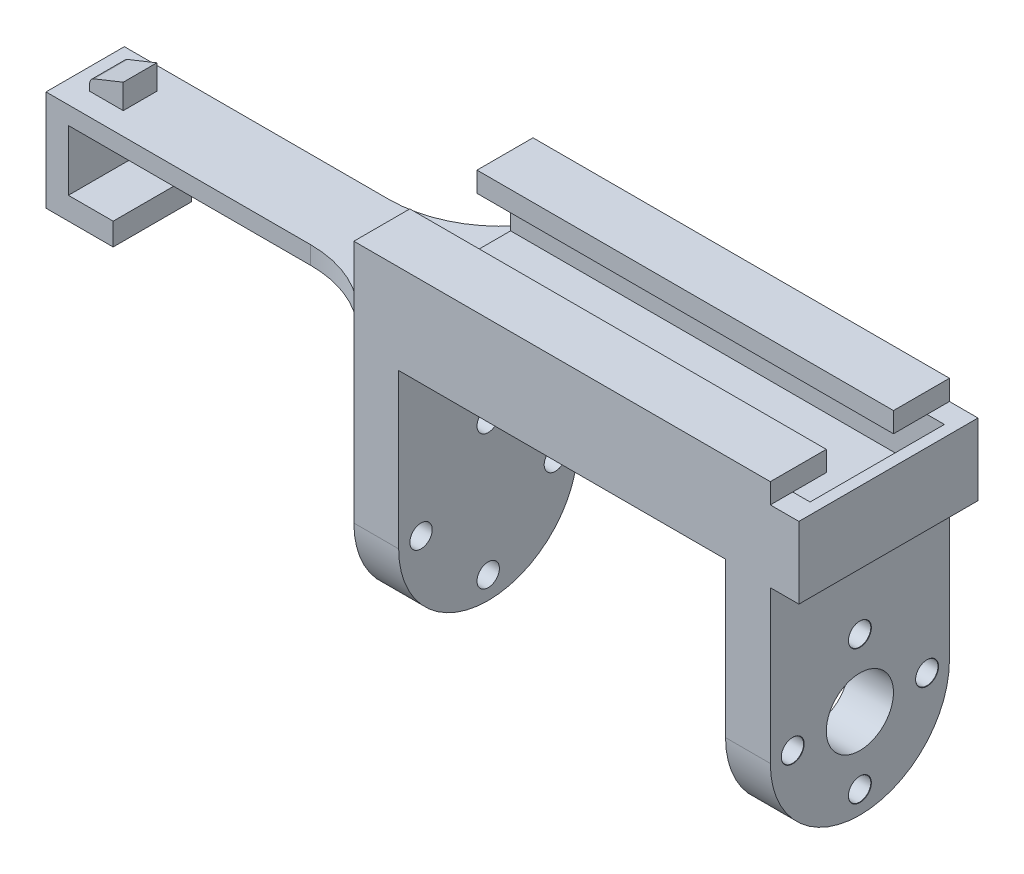
SolidWorks part; units mm, degrees
ref_plane "Front Plane" through (0, 0, 0) normal (0, 0, 1) x (1, 0, 0)
ref_plane "Top Plane" through (0, 0, 0) normal (0, 1, 0) x (1, 0, 0)
ref_plane "Right Plane" through (0, 0, 0) normal (1, 0, 0) x (0, 0, -1)
sketch "Sketch1" plane through (0, 0, 0) normal (0, 0, 1) x (1, 0, 0)
  line L1 (-18.6, 18) -> (18.6, 18)
  line L2 (-18.6, 18) -> (-18.6, -18)
  line L3 (-18.6, -18) -> (18.6, -18)
  line L4 (18.6, 18) -> (18.6, -18)
  line L5 (-18.6, 18) -> (18.6, -18) construction
  line L6 (-18.6, -18) -> (18.6, 18) construction
  line L7 (-14.6, -18) -> (14.6, -18)
  line L8 (-14.6, -18) -> (-14.6, 10)
  line L9 (-14.6, 10) -> (14.6, 10)
  line L10 (14.6, -18) -> (14.6, 10)
  point P0 (0, 0)
  point P10 (0, 10)
  dimension "D1" = 29.2
  dimension "D2" = 4
  dimension "D3" = 28
  dimension "D4" = 8
extrude "Boss-Extrude1" add sketch "Sketch1" along normal blind 8 and the other way blind 8 contours L10 L3 L4 L1 L2 L8 L9 region at (0, 17.4823, 0)
sketch "Sketch2" plane through (18.6, 0, 0) normal (1, 0, 0) x (0, 0, -1)
  circle A0 centre (0, -3.8) radius 6 construction
  point P2 (0, -9.8)
  point P4 (6, -3.8)
  point P5 (0, 2.2)
  point P6 (-6, -3.8)
  dimension "D2" = 12
  dimension "D1" = 3.8
hole_wizard "M1.6 Clearance Hole1" positions "Sketch3" profile "Sketch4" hole size "M1.6" standard "ANSI Metric"
sketch "Sketch3" plane through (18.6, 0, 0) normal (1, 0, 0) x (0, 0, -1)
  point P0 (-6, -3.8)
  point P3 (0, 2.2)
  point P6 (6, -3.8)
  point P9 (0, -9.8)
sketch "Sketch4" plane through (18.6, -3.8, 6) normal (0, 1, 0) x (0, 0, -1)
  line L0 (0, 0) -> (0, 4.6009)
  line L1 (0, 4.6009) -> (1, 4)
  line L2 (1, 4) -> (1, 0.025)
  line L3 (1, 0.025) -> (1.025, 0)
  line L5 (1.025, 0) -> (0, 0)
  line L6 (-1, 0.025) -> (-1.025, 0) construction
  line L10 (0, 4.6009) -> (-1, 4) construction
  line L11 (0, -6.35) -> (0, 107.95) construction
  dimension "Hole Dia." = 2
  dimension "Hole Depth" = 4
  dimension "Near C'Sink Dia." = 2.05
  dimension "Near C'Sink Angle" = 90
  dimension "Drill Angle" = 118
mirror "Mirror1" about plane through (0, 0, 0) normal (1, 0, 0) of "M1.6 Clearance Hole1"
sketch "Sketch5" plane through (18.6, 0, 0) normal (1, 0, 0) x (0, 0, -1)
  line L4 (8, 18) -> (-8, 18)
  line L5 (-8, 18) -> (-8, -18)
  line L6 (-8, -18) -> (8, -18)
  line L7 (8, -18) -> (8, 18)
  line L9 (-8, -3.8) -> (-8, -18)
  line L10 (-8, -18) -> (8, -18)
  line L11 (8, -18) -> (8, -3.8)
  arc A0 (-8, -3.8) -> (8, -3.8) centre (0, -3.8) ccw
  dimension "D1" = 16
  dimension "D2" = 0
extrude "Cut-Extrude1" cut sketch "Sketch5" against normal through all both and the other way through all
sketch "Sketch6" plane through (-18.6, 0, 0) normal (-1, 0, 0) x (0, 0, 1)
  line L0 (-8, 10) -> (8, 10) construction
  line L1 (-8, 10) -> (8, 10) construction
  line L2 (-8, 18) -> (8, 18) construction
  line L3 (-6, 11.8) -> (6, 11.8)
  line L4 (-6, 11.8) -> (-6, 16.2)
  line L5 (-6, 16.2) -> (6, 16.2)
  line L6 (6, 11.8) -> (6, 16.2)
  line L7 (-3, 16.2) -> (3, 16.2)
  line L8 (-3, 16.2) -> (-3, 18)
  line L9 (-3, 18) -> (3, 18)
  line L10 (3, 16.2) -> (3, 18)
  line L11 (8, 18) -> (8, -3.8) construction
  point P12 (0, 11.8)
  point P14 (0, 18)
  line M12 (8, 18) -> (-8, 18)
  dimension "D1" = 2
  dimension "D2" = 1.8
  dimension "D3" = 1.8
  dimension "D4" = 6
extrude "Cut-Extrude2" cut sketch "Sketch6" against normal through all both contours L5 L10 L8 M12 | L3 L6 L5 L4 region at (-18.6, 14, 0) region at (-18.6, 17.1, 0)
sketch "Sketch8" plane through (0, 11.8, 0) normal (0, 1, 0) x (1, 0, 0)
  line L1 (-18.6, -3.5) -> (-48.6, -3.5)
  line L2 (-18.6, -3.5) -> (-18.6, 3.5)
  line L3 (-18.6, 3.5) -> (-48.6, 3.5)
  line L4 (-48.6, -3.5) -> (-48.6, 3.5)
  line L5 (-18.6, 6) -> (-18.6, -6) construction
  point P9 (-18.6, 0)
  point P10 (-18.6, 0)
  dimension "D1" = 7
  dimension "D2" = 30
extrude "Boss-Extrude2" add sketch "Sketch8" against normal blind 1.6 from offset 0.5 contours L4 | L4 region at (-33.6, 11.8, 0) offset against normal yes
sketch "Sketch10" plane through (0, 0, 3.5) normal (0, 0, 1) x (1, 0, 0)
  line L0 (-48.6, 11.3) -> (-50.6, 11.3)
  line L1 (-50.6, 11.3) -> (-50.6, 2.3)
  line L2 (-50.6, 2.3) -> (-44.6, 2.3)
  line L3 (-44.6, 2.3) -> (-44.6, 4.3)
  line L4 (-44.6, 4.3) -> (-48.6, 4.3)
  line L5 (-48.6, 4.3) -> (-48.6, 11.3)
  line L7 (-48.6, 9.7) -> (-48.6, 11.3) construction
  dimension "D1" = 2
  dimension "D2" = 4
  dimension "D3" = 7
extrude "Boss-Extrude3" add sketch "Sketch10" against normal up to surface (7 mm away) up to face at (-33.6, 10.5, -3.5)
sketch "Sketch12" plane through (18.6, 0, 0) normal (1, 0, 0) x (0, 0, -1)
  line L0 (6, 11.8) -> (6, 16.2) construction
  line L1 (6, 11.8) -> (-6, 11.8) construction
  line L2 (-6, 11.8) -> (-6, 16.2) construction
  line L3 (6, 11.8) -> (6, 16.2)
  line L4 (6, 11.8) -> (-6, 11.8)
  line L5 (-6, 11.8) -> (-6, 16.2)
  line L6 (6, 16.2) -> (8, 16.2)
  line L7 (8, 18) -> (8, -3.8) construction
  line L8 (8, 16.2) -> (8, 9.8)
  line L9 (8, 9.8) -> (-8, 9.8)
  line L10 (-8, 18) -> (-8, -3.8) construction
  line L11 (-8, 9.8) -> (-8, 16.2)
  line L12 (-8, 16.2) -> (-6, 16.2)
  dimension "D1" = 2
extrude "Boss-Extrude4" add sketch "Sketch12" along normal offset from surface (1.55 mm away) 0.15 contours L12 L5 L4 L3 L6 L8 L9 L11 offset beyond the face yes
sketch "Sketch13" plane through (20.15, 0, 0) normal (1, 0, 0) x (0, 0, -1)
  line L0 (-8, 16.2) -> (8, 16.2)
  line L8 (-8, 16.2) -> (-8, 9.8)
  line L9 (-8, 9.8) -> (8, 9.8)
  line L10 (8, 9.8) -> (8, 16.2)
  line L11 (8, 16.2) -> (6, 16.2)
  line L12 (6, 16.2) -> (6, 11.8)
  line L13 (6, 11.8) -> (-6, 11.8)
  line L14 (-6, 11.8) -> (-6, 16.2)
  line L15 (-6, 16.2) -> (-8, 16.2)
  line L16 (-8, 16.2) -> (-8, 9.8)
  line L17 (-8, 9.8) -> (8, 9.8)
  line L18 (8, 9.8) -> (8, 16.2)
  dimension "D1" = 0
extrude "Boss-Extrude5" add sketch "Sketch13" along normal blind 1
sketch "Sketch14" plane through (0, 0, 0) normal (0, 0, 1) x (1, 0, 0)
  line L0 (-48.7, 11.3) -> (-48.7, 12.3)
  line L1 (-18.6, 11.3) -> (-50.6, 11.3) construction
  line L2 (-48.7, 12.3) -> (-45.7, 13.5)
  line L3 (-45.7, 13.5) -> (-45.7, 11.3)
  line L4 (-50.6, 11.3) -> (-50.6, 2.3) construction
  line L5 (-45.7, 11.3) -> (-48.7, 11.3)
  dimension "D1" = 2.2
  dimension "D2" = 1.9
  dimension "D3" = 3
  dimension "D4" = 1
extrude "Boss-Extrude6" add sketch "Sketch14" along normal blind 1.5 and the other way blind 1.5
fillet "Fillet1" radius 0.6 1 edges at (-48.7, 12.3, 0)
sketch "Sketch15" plane through (0, 0, 0) normal (0, 0, 1) x (1, 0, 0)
  line L0 (-14.6, -3.8) -> (14.6, -3.8) construction
  point P4 (0, -3.8)
fillet "Fillet2" radius 10 2 edges at (-18.6, 10.5, -3.5) (-18.6, 10.5, 3.5)
fillet "Fillet3" radius 3 1 edges at (-18.6, 9.7, 0)
sketch "Sketch16" plane through (18.6, 0, 0) normal (1, 0, 0) x (0, 0, -1)
  circle A0 centre (0, -3.8) radius 3
  dimension "D1" = 6
extrude "Cut-Extrude3" cut sketch "Sketch16" against normal blind 10 and the other way through all
